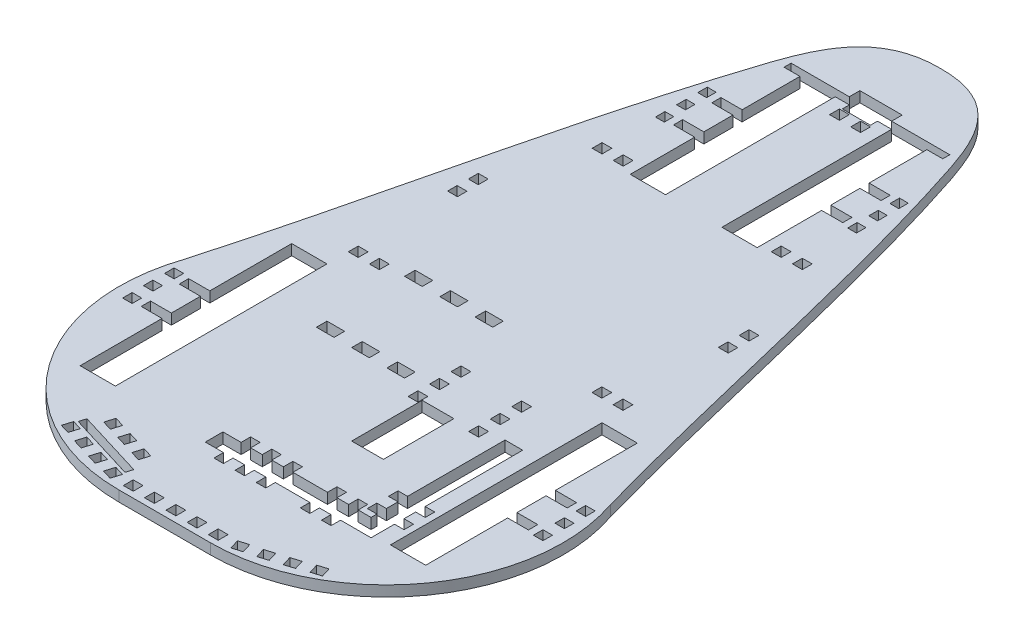
SolidWorks part; units mm, degrees
ref_plane "Front Plane" through (0, 0, 0) normal (0, 0, 1) x (1, 0, 0)
ref_plane "Top Plane" through (0, 0, 0) normal (0, 1, 0) x (1, 0, 0)
ref_plane "Right Plane" through (0, 0, 0) normal (1, 0, 0) x (0, 0, -1)
sketch "Sketch1" plane through (0, 0, 0) normal (0, 1, 0) x (1, 0, 0)
  line L0 (54.872, 210.7624) -> (54.872, -9.2376) construction
  line L1 (41.9035, -9.2376) -> (67.8405, -9.2376)
  line L6 (5.872, 75.7624) -> (15.872, 75.7624)
  line L7 (54.872, -9.2376) -> (64.872, -9.2376)
  line L8 (54.872, -9.2376) -> (44.872, -9.2376)
  line L9 (5.872, 75.7624) -> (5.872, 15.7624)
  line L10 (5.872, 15.7624) -> (15.872, 15.7624)
  line L11 (15.872, 75.7624) -> (15.872, 15.7624)
  line L12 (5.872, 75.7624) -> (15.872, 15.7624) construction
  line L13 (5.872, 15.7624) -> (15.872, 75.7624) construction
  line L18 (-0.128, 52.5374) -> (5.872, 52.5374)
  line L19 (-0.128, 52.5374) -> (-0.128, 49.8874)
  line L35 (103.872, 15.7624) -> (93.872, 15.7624)
  line L36 (93.872, 75.7624) -> (93.872, 15.7624)
  line L37 (103.872, 75.7624) -> (93.872, 75.7624)
  line L38 (103.872, 75.7624) -> (103.872, 15.7624)
  line L40 (36.872, 190.7624) -> (46.872, 190.7624)
  line L41 (36.872, 190.7624) -> (36.872, 140.7624)
  line L42 (36.872, 140.7624) -> (46.872, 140.7624)
  line L43 (46.872, 190.7624) -> (46.872, 140.7624)
  line L44 (36.872, 190.7624) -> (46.872, 140.7624) construction
  line L45 (36.872, 140.7624) -> (46.872, 190.7624) construction
  line L46 (10.872, 45.7624) -> (-10.2667, 45.7624) construction
  line L63 (72.872, 140.7624) -> (62.872, 140.7624)
  line L64 (62.872, 190.7624) -> (62.872, 140.7624)
  line L65 (72.872, 190.7624) -> (62.872, 190.7624)
  line L66 (72.872, 190.7624) -> (72.872, 140.7624)
  line L78 (114.572, 47.1124) -> (111.872, 44.4124) construction
  line L79 (114.572, 44.4124) -> (111.872, 47.1124) construction
  line L80 (114.572, 50.4124) -> (111.872, 53.1124) construction
  line L81 (114.572, 53.1124) -> (111.872, 50.4124) construction
  line L82 (109.7728, 38.9874) -> (103.7728, 41.6374) construction
  line L83 (109.7728, 41.6374) -> (103.7728, 38.9874) construction
  line L84 (109.872, 49.8874) -> (103.872, 52.5374) construction
  line L85 (109.872, 52.5374) -> (103.872, 49.8874) construction
  line L86 (111.7728, 41.1124) -> (111.7728, 38.4124)
  line L87 (114.4728, 38.4124) -> (111.7728, 38.4124)
  line L88 (114.4728, 41.1124) -> (114.4728, 38.4124)
  line L89 (111.872, 44.4124) -> (111.872, 47.1124)
  line L90 (114.572, 47.1124) -> (111.872, 47.1124)
  line L91 (114.572, 44.4124) -> (114.572, 47.1124)
  line L92 (41.872, 165.7624) -> (24.9145, 165.7624) construction
  line L93 (30.872, 172.4874) -> (36.872, 172.4874)
  line L94 (30.872, 172.4874) -> (30.872, 169.8874)
  line L95 (30.872, 169.8874) -> (36.872, 169.8874)
  line L96 (36.872, 172.4874) -> (36.872, 169.8874)
  line L97 (30.872, 172.4874) -> (36.872, 169.8874) construction
  line L98 (30.872, 169.8874) -> (36.872, 172.4874) construction
  line L103 (26.372, 161.1124) -> (28.872, 161.1124)
  line L104 (26.372, 173.1124) -> (28.872, 173.1124)
  line L105 (30.872, 161.6374) -> (36.872, 161.6374)
  line L106 (30.872, 161.6374) -> (30.872, 159.0374)
  line L107 (30.872, 159.0374) -> (36.872, 159.0374)
  line L108 (36.872, 161.6374) -> (36.872, 159.0374)
  line L109 (30.872, 161.6374) -> (36.872, 159.0374) construction
  line L110 (30.872, 159.0374) -> (36.872, 161.6374) construction
  line L111 (26.372, 173.1124) -> (26.372, 170.4124)
  line L112 (26.372, 170.4124) -> (28.872, 170.4124)
  line L113 (28.872, 173.1124) -> (28.872, 170.4124)
  line L114 (26.372, 173.1124) -> (28.872, 170.4124) construction
  line L115 (26.372, 170.4124) -> (28.872, 173.1124) construction
  line L116 (26.372, 164.4124) -> (28.872, 164.4124)
  line L117 (26.372, 164.4124) -> (26.372, 167.1124)
  line L118 (26.372, 167.1124) -> (28.872, 167.1124)
  line L119 (28.872, 164.4124) -> (28.872, 167.1124)
  line L120 (26.372, 164.4124) -> (28.872, 167.1124) construction
  line L121 (26.372, 167.1124) -> (28.872, 164.4124) construction
  line L122 (26.372, 161.1124) -> (26.372, 158.4124)
  line L123 (26.372, 158.4124) -> (28.872, 158.4124)
  line L124 (28.872, 161.1124) -> (28.872, 158.4124)
  line L125 (83.372, 167.1124) -> (80.872, 164.4124) construction
  line L126 (83.372, 164.4124) -> (80.872, 167.1124) construction
  line L127 (83.372, 170.4124) -> (80.872, 173.1124) construction
  line L128 (83.372, 173.1124) -> (80.872, 170.4124) construction
  line L129 (78.872, 159.0374) -> (72.872, 161.6374) construction
  line L130 (78.872, 161.6374) -> (72.872, 159.0374) construction
  line L131 (78.872, 169.8874) -> (72.872, 172.4874) construction
  line L132 (78.872, 172.4874) -> (72.872, 169.8874) construction
  line L133 (80.872, 161.1124) -> (80.872, 158.4124)
  line L134 (83.372, 158.4124) -> (80.872, 158.4124)
  line L135 (83.372, 161.1124) -> (83.372, 158.4124)
  line L136 (80.872, 164.4124) -> (80.872, 167.1124)
  line L137 (83.372, 167.1124) -> (80.872, 167.1124)
  line L138 (83.372, 164.4124) -> (83.372, 167.1124)
  line L139 (83.372, 164.4124) -> (80.872, 164.4124)
  line L140 (80.872, 173.1124) -> (80.872, 170.4124)
  line L141 (83.372, 170.4124) -> (80.872, 170.4124)
  line L142 (83.372, 173.1124) -> (83.372, 170.4124)
  line L143 (72.872, 161.6374) -> (72.872, 159.0374)
  line L144 (78.872, 159.0374) -> (72.872, 159.0374)
  line L145 (78.872, 161.6374) -> (78.872, 159.0374)
  line L146 (78.872, 161.6374) -> (72.872, 161.6374)
  line L147 (83.372, 173.1124) -> (80.872, 173.1124)
  line L148 (83.372, 161.1124) -> (80.872, 161.1124)
  line L149 (72.872, 172.4874) -> (72.872, 169.8874)
  line L150 (78.872, 169.8874) -> (72.872, 169.8874)
  line L151 (78.872, 172.4874) -> (78.872, 169.8874)
  line L152 (78.872, 172.4874) -> (72.872, 172.4874)
  line L153 (-0.128, 49.8874) -> (5.872, 49.8874)
  line L154 (5.872, 52.5374) -> (5.872, 49.8874)
  line L155 (-0.128, 52.5374) -> (5.872, 49.8874) construction
  line L156 (-0.128, 49.8874) -> (5.872, 52.5374) construction
  line L157 (-4.7289, 41.1124) -> (-2.0289, 41.1124)
  line L158 (-4.828, 53.1124) -> (-2.128, 53.1124)
  line L159 (-0.0289, 41.6374) -> (5.9711, 41.6374)
  line L160 (-0.0289, 41.6374) -> (-0.0289, 38.9874)
  line L161 (-0.0289, 38.9874) -> (5.9711, 38.9874)
  line L162 (5.9711, 41.6374) -> (5.9711, 38.9874)
  line L163 (-0.0289, 41.6374) -> (5.9711, 38.9874) construction
  line L164 (-0.0289, 38.9874) -> (5.9711, 41.6374) construction
  line L165 (-4.828, 53.1124) -> (-4.828, 50.4124)
  line L166 (-4.828, 50.4124) -> (-2.128, 50.4124)
  line L167 (-2.128, 53.1124) -> (-2.128, 50.4124)
  line L168 (-4.828, 53.1124) -> (-2.128, 50.4124) construction
  line L169 (-4.828, 50.4124) -> (-2.128, 53.1124) construction
  line L170 (-4.828, 44.4124) -> (-2.128, 44.4124)
  line L171 (-4.828, 44.4124) -> (-4.828, 47.1124)
  line L172 (-4.828, 47.1124) -> (-2.128, 47.1124)
  line L173 (-2.128, 44.4124) -> (-2.128, 47.1124)
  line L174 (-4.828, 44.4124) -> (-2.128, 47.1124) construction
  line L175 (-4.828, 47.1124) -> (-2.128, 44.4124) construction
  line L176 (-4.7289, 41.1124) -> (-4.7289, 38.4124)
  line L177 (-4.7289, 38.4124) -> (-2.0289, 38.4124)
  line L178 (-2.0289, 41.1124) -> (-2.0289, 38.4124)
  line L179 (114.572, 44.4124) -> (111.872, 44.4124)
  line L180 (111.872, 53.1124) -> (111.872, 50.4124)
  line L181 (114.572, 50.4124) -> (111.872, 50.4124)
  line L182 (114.572, 53.1124) -> (114.572, 50.4124)
  line L183 (103.7728, 41.6374) -> (103.7728, 38.9874)
  line L184 (109.7728, 38.9874) -> (103.7728, 38.9874)
  line L185 (109.7728, 41.6374) -> (109.7728, 38.9874)
  line L186 (109.7728, 41.6374) -> (103.7728, 41.6374)
  line L187 (114.572, 53.1124) -> (111.872, 53.1124)
  line L188 (114.4728, 41.1124) -> (111.7728, 41.1124)
  line L189 (103.872, 52.5374) -> (103.872, 49.8874)
  line L190 (109.872, 49.8874) -> (103.872, 49.8874)
  line L191 (109.872, 52.5374) -> (109.872, 49.8874)
  line L192 (109.872, 52.5374) -> (103.872, 52.5374)
  line L193 (103.872, 45.7624) -> (5.872, 45.7624) construction
  line L200 (62.872, 55.7624) -> (71.872, 55.7624)
  line L201 (62.872, 55.7624) -> (62.872, 35.7624)
  line L202 (62.872, 35.7624) -> (71.872, 35.7624)
  line L203 (71.872, 55.7624) -> (71.872, 35.7624)
  line L204 (62.872, 55.7624) -> (71.872, 35.7624) construction
  line L205 (62.872, 35.7624) -> (71.872, 55.7624) construction
  line L211 (39.9211, 61.7172) -> (44.9211, 61.7172)
  line L213 (59.9211, 69.7172) -> (62.7211, 69.7172)
  line L214 (59.9211, 57.5172) -> (62.7211, 57.5172)
  line L215 (59.9211, 57.5172) -> (59.9211, 54.7172)
  line L216 (59.9211, 54.7172) -> (62.7211, 54.7172)
  line L217 (62.7211, 57.5172) -> (62.7211, 54.7172)
  line L218 (59.9211, 57.5172) -> (62.7211, 54.7172) construction
  line L219 (59.9211, 54.7172) -> (62.7211, 57.5172) construction
  line L220 (59.9211, 69.7172) -> (59.9211, 66.9172)
  line L221 (59.9211, 66.9172) -> (62.7211, 66.9172)
  line L222 (62.7211, 69.7172) -> (62.7211, 66.9172)
  line L223 (59.9211, 63.6172) -> (62.7211, 63.6172)
  line L224 (59.9211, 63.6172) -> (59.9211, 60.8172)
  line L225 (59.9211, 60.8172) -> (62.7211, 60.8172)
  line L226 (62.7211, 63.6172) -> (62.7211, 60.8172)
  line L227 (77.1211, 69.7172) -> (79.9211, 69.7172)
  line L228 (77.1211, 57.5172) -> (79.9211, 57.5172)
  line L229 (77.1211, 57.5172) -> (77.1211, 54.7172)
  line L230 (77.1211, 54.7172) -> (79.9211, 54.7172)
  line L231 (79.9211, 57.5172) -> (79.9211, 54.7172)
  line L232 (77.1211, 69.7172) -> (77.1211, 66.9172)
  line L233 (77.1211, 66.9172) -> (79.9211, 66.9172)
  line L234 (79.9211, 69.7172) -> (79.9211, 66.9172)
  line L235 (77.1211, 63.6172) -> (79.9211, 63.6172)
  line L236 (77.1211, 63.6172) -> (77.1211, 60.8172)
  line L237 (77.1211, 60.8172) -> (79.9211, 60.8172)
  line L238 (79.9211, 63.6172) -> (79.9211, 60.8172)
  line L244 (49.9211, 61.7172) -> (54.9211, 61.7172)
  line L245 (49.9211, 61.7172) -> (49.9211, 58.7172)
  line L246 (49.9211, 58.7172) -> (54.9211, 58.7172)
  line L247 (54.9211, 61.7172) -> (54.9211, 58.7172)
  line L248 (49.9211, 61.7172) -> (54.9211, 58.7172) construction
  line L249 (49.9211, 58.7172) -> (54.9211, 61.7172) construction
  line L250 (39.9211, 61.7172) -> (39.9211, 58.7172)
  line L251 (39.9211, 58.7172) -> (44.9211, 58.7172)
  line L252 (44.9211, 61.7172) -> (44.9211, 58.7172)
  line L253 (29.9211, 61.7172) -> (34.9211, 61.7172)
  line L254 (29.9211, 61.7172) -> (29.9211, 58.7172)
  line L255 (29.9211, 58.7172) -> (34.9211, 58.7172)
  line L256 (34.9211, 61.7172) -> (34.9211, 58.7172)
  line L257 (49.9211, 86.7172) -> (54.9211, 86.7172)
  line L258 (49.9211, 86.7172) -> (49.9211, 83.7172)
  line L259 (49.9211, 83.7172) -> (54.9211, 83.7172)
  line L260 (54.9211, 86.7172) -> (54.9211, 83.7172)
  line L261 (39.9211, 86.7172) -> (44.9211, 86.7172)
  line L262 (39.9211, 86.7172) -> (39.9211, 83.7172)
  line L263 (39.9211, 83.7172) -> (44.9211, 83.7172)
  line L264 (44.9211, 86.7172) -> (44.9211, 83.7172)
  line L265 (29.9211, 86.7172) -> (34.9211, 86.7172)
  line L266 (29.9211, 86.7172) -> (29.9211, 83.7172)
  line L267 (29.9211, 83.7172) -> (34.9211, 83.7172)
  line L268 (34.9211, 86.7172) -> (34.9211, 83.7172)
  line L279 (15.072, 113.4624) -> (17.872, 113.4624)
  line L284 (15.0729, 119.4624) -> (17.8729, 119.4624)
  line L285 (15.0729, 119.4624) -> (15.0729, 116.6624)
  line L286 (15.0729, 116.6624) -> (17.8729, 116.6624)
  line L287 (17.8729, 119.4624) -> (17.8729, 116.6624)
  line L288 (15.072, 113.4624) -> (15.072, 110.7624)
  line L289 (15.072, 110.7624) -> (17.872, 110.7624)
  line L290 (17.872, 113.4624) -> (17.872, 110.7624)
  line L291 (287.5426, 108.3221) -> (290.3426, 108.3221)
  line L292 (212.3426, 111.3221) -> (290.3426, 111.3221)
  line L293 (212.3426, 111.3221) -> (212.3426, 29.7221)
  line L294 (212.3426, 29.7221) -> (290.3426, 29.7221)
  line L295 (290.3426, 111.3221) -> (290.3426, 29.7221)
  line L296 (212.3426, 108.3221) -> (215.1426, 108.3221)
  line L297 (212.3426, 108.3221) -> (212.3426, 105.5221)
  line L298 (212.3426, 105.5221) -> (215.1426, 105.5221)
  line L299 (215.1426, 108.3221) -> (215.1426, 105.5221)
  line L300 (287.5426, 108.3221) -> (287.5426, 105.5221)
  line L301 (287.5426, 105.5221) -> (290.3426, 105.5221)
  line L302 (290.3426, 108.3221) -> (290.3426, 105.5221)
  line L303 (218.3426, 108.3221) -> (221.1426, 108.3221)
  line L304 (218.3426, 108.3221) -> (218.3426, 105.5221)
  line L305 (218.3426, 105.5221) -> (221.1426, 105.5221)
  line L306 (221.1426, 108.3221) -> (221.1426, 105.5221)
  line L307 (281.5426, 84.5298) -> (284.3426, 84.5298)
  line L308 (281.5426, 84.5298) -> (281.5426, 81.7298)
  line L309 (281.5426, 81.7298) -> (284.3426, 81.7298)
  line L310 (284.3426, 84.5298) -> (284.3426, 81.7298)
  line L311 (287.5426, 35.5221) -> (290.3426, 35.5221)
  line L312 (212.3426, 35.5221) -> (215.1426, 35.5221)
  line L313 (212.3426, 35.5221) -> (212.3426, 32.7221)
  line L314 (212.3426, 32.7221) -> (215.1426, 32.7221)
  line L315 (215.1426, 35.5221) -> (215.1426, 32.7221)
  line L316 (287.5426, 35.5221) -> (287.5426, 32.7221)
  line L317 (287.5426, 32.7221) -> (290.3426, 32.7221)
  line L318 (290.3426, 35.5221) -> (290.3426, 32.7221)
  line L319 (218.3426, 35.5221) -> (221.1426, 35.5221)
  line L320 (218.3426, 35.5221) -> (218.3426, 32.7221)
  line L321 (218.3426, 32.7221) -> (221.1426, 32.7221)
  line L322 (221.1426, 35.5221) -> (221.1426, 32.7221)
  line L323 (281.5426, 35.5221) -> (284.3426, 35.5221)
  line L324 (281.5426, 35.5221) -> (281.5426, 32.7221)
  line L325 (281.5426, 32.7221) -> (284.3426, 32.7221)
  line L326 (284.3426, 35.5221) -> (284.3426, 32.7221)
  line L332 (15.9201, 84.5624) -> (18.7201, 84.5624)
  line L333 (15.9201, 84.5624) -> (15.9201, 81.7624)
  line L334 (15.9201, 81.7624) -> (18.7201, 81.7624)
  line L335 (18.7201, 84.5624) -> (18.7201, 81.7624)
  line L339 (21.9201, 84.5624) -> (24.7201, 84.5624)
  line L340 (21.9201, 84.5624) -> (21.9201, 81.7624)
  line L341 (21.9201, 81.7624) -> (24.7201, 81.7624)
  line L342 (24.7201, 84.5624) -> (24.7201, 81.7624)
  line L363 (25.072, 144.5629) -> (27.872, 144.5629)
  line L368 (25.072, 144.5629) -> (25.072, 141.7629)
  line L369 (25.072, 141.7629) -> (27.872, 141.7629)
  line L370 (27.872, 144.5629) -> (27.872, 141.7629)
  line L371 (31.072, 144.5624) -> (33.872, 144.5624)
  line L372 (31.072, 144.5624) -> (31.072, 141.7624)
  line L373 (31.072, 141.7624) -> (33.872, 141.7624)
  line L374 (33.872, 144.5624) -> (33.872, 141.7624)
  line L375 (75.872, 144.5624) -> (75.872, 141.7624)
  line L376 (78.672, 141.7624) -> (75.872, 141.7624)
  line L377 (78.672, 144.5624) -> (78.672, 141.7624)
  line L378 (78.672, 144.5624) -> (75.872, 144.5624)
  line L379 (81.872, 144.5629) -> (81.872, 141.7629)
  line L380 (84.672, 141.7629) -> (81.872, 141.7629)
  line L381 (84.672, 144.5629) -> (84.672, 141.7629)
  line L382 (84.672, 144.5629) -> (81.872, 144.5629)
  line L383 (50.4739, 186.4794) -> (50.472, 183.6794)
  line L384 (32.372, 190.884) -> (77.372, 190.884)
  line L385 (32.372, 190.884) -> (32.372, 188.884)
  line L386 (32.372, 188.884) -> (77.372, 188.884)
  line L387 (77.372, 190.884) -> (77.372, 188.884)
  line L388 (48.872, 193.884) -> (60.872, 193.884)
  line L389 (48.872, 193.884) -> (48.872, 190.884)
  line L390 (48.872, 190.884) -> (60.872, 190.884)
  line L391 (60.872, 193.884) -> (60.872, 190.884)
  line L392 (53.272, 183.6794) -> (50.472, 183.6794)
  line L393 (53.272, 186.4794) -> (53.272, 183.6794)
  line L394 (53.272, 186.4794) -> (50.4739, 186.4794)
  line L404 (85.372, 55.7624) -> (88.372, 55.7624)
  line L405 (85.372, 55.7624) -> (85.372, 15.7624)
  line L406 (85.372, 15.7624) -> (88.372, 15.7624)
  line L407 (88.372, 55.7624) -> (88.372, 15.7624)
  line L408 (44.372, 18.7624) -> (88.372, 18.7624)
  line L409 (44.372, 18.7624) -> (44.372, 15.7624)
  line L410 (44.372, 15.7624) -> (88.372, 15.7624)
  line L411 (88.372, 18.7624) -> (88.372, 15.7624)
  line L471 (41.9035, -9.2376) -> (64.872, -9.2376)
  line L480 (47.522, 22.4624) -> (47.522, 19.7624)
  line L481 (50.222, 19.7624) -> (47.522, 19.7624)
  line L482 (50.222, 22.4624) -> (50.222, 19.7624)
  line L483 (50.222, 22.4624) -> (47.522, 22.4624)
  line L484 (53.522, 22.4624) -> (53.522, 19.7624)
  line L485 (56.222, 19.7624) -> (53.522, 19.7624)
  line L486 (56.222, 22.4624) -> (56.222, 19.7624)
  line L487 (56.222, 22.4624) -> (53.522, 22.4624)
  line L488 (59.522, 22.4624) -> (59.522, 19.7624)
  line L489 (62.222, 19.7624) -> (59.522, 19.7624)
  line L490 (62.222, 22.4624) -> (62.222, 19.7624)
  line L491 (62.222, 22.4624) -> (59.522, 22.4624)
  line L492 (56.472, 186.4794) -> (59.2701, 186.4794)
  line L493 (56.472, 186.4794) -> (56.472, 183.6794)
  line L494 (56.472, 183.6794) -> (59.272, 183.6794)
  line L495 (59.2701, 186.4794) -> (59.272, 183.6794)
  line L496 (94.672, 113.4624) -> (94.672, 110.7624)
  line L497 (94.672, 110.7624) -> (91.872, 110.7624)
  line L498 (91.872, 113.4624) -> (91.872, 110.7624)
  line L499 (94.672, 113.4624) -> (91.872, 113.4624)
  line L500 (94.671, 119.4624) -> (94.671, 116.6624)
  line L501 (94.671, 116.6624) -> (91.871, 116.6624)
  line L502 (91.871, 119.4624) -> (91.871, 116.6624)
  line L503 (94.671, 119.4624) -> (91.871, 119.4624)
  line L512 (87.8238, 84.5624) -> (87.8238, 81.7624)
  line L513 (87.8238, 81.7624) -> (85.0238, 81.7624)
  line L514 (85.0238, 84.5624) -> (85.0238, 81.7624)
  line L515 (87.8238, 84.5624) -> (85.0238, 84.5624)
  line L516 (93.8238, 84.5624) -> (93.8238, 81.7624)
  line L517 (93.8238, 81.7624) -> (91.0238, 81.7624)
  line L518 (91.0238, 84.5624) -> (91.0238, 81.7624)
  line L519 (93.8238, 84.5624) -> (91.0238, 84.5624)
  line L520 (76.372, 18.7624) -> (76.372, 15.7624) construction
  line L521 (64.372, 18.7624) -> (88.372, 18.7624)
  line L522 (64.372, 18.7624) -> (64.372, 15.7624)
  line L523 (64.372, 15.7624) -> (88.372, 15.7624)
  line L524 (88.372, 18.7624) -> (88.372, 15.7624)
  line L525 (76.372, 27.5136) -> (76.372, 8.1564) construction
  line L526 (85.372, 25.7624) -> (88.372, 25.7624) construction
  line L527 (85.372, 35.7624) -> (88.372, 35.7624)
  line L528 (85.372, 35.7624) -> (85.372, 15.7624)
  line L529 (85.372, 15.7624) -> (88.372, 15.7624)
  line L530 (88.372, 35.7624) -> (88.372, 15.7624)
  line L531 (91.4767, 25.7624) -> (69.6189, 25.7624) construction
  line L532 (44.372, 17.2624) -> (64.372, 17.2624) construction
  line L537 (84.372, 57.7624) -> (89.372, 57.7624)
  line L538 (84.372, 57.7624) -> (84.372, 14.7624)
  line L539 (84.372, 14.7624) -> (89.372, 14.7624)
  line L540 (89.372, 57.7624) -> (89.372, 14.7624)
  line L541 (42.372, 19.7624) -> (89.372, 19.7624)
  line L542 (42.372, 19.7624) -> (42.372, 14.7624)
  line L543 (42.372, 14.7624) -> (89.372, 14.7624)
  line L544 (89.372, 19.7624) -> (89.372, 14.7624)
  line L545 (74.722, 14.7624) -> (74.722, 12.0624)
  line L546 (74.722, 12.0624) -> (72.022, 12.0624)
  line L547 (72.022, 14.7624) -> (72.022, 12.0624)
  line L548 (74.722, 14.7624) -> (72.022, 14.7624)
  line L553 (80.722, 14.7624) -> (80.722, 12.0624)
  line L554 (78.022, 14.7624) -> (80.722, 14.7624)
  line L555 (78.022, 14.7624) -> (78.022, 12.0624)
  line L556 (78.022, 12.0624) -> (80.722, 12.0624)
  line L557 (64.372, 17.2624) -> (88.372, 17.2624) construction
  line L558 (78.022, 19.7624) -> (80.722, 19.7624)
  line L559 (78.022, 19.7624) -> (78.022, 22.4624)
  line L560 (78.022, 22.4624) -> (80.722, 22.4624)
  line L561 (80.722, 19.7624) -> (80.722, 22.4624)
  line L562 (72.022, 19.7624) -> (72.022, 22.4624)
  line L563 (74.722, 19.7624) -> (72.022, 19.7624)
  line L564 (74.722, 19.7624) -> (74.722, 22.4624)
  line L565 (74.722, 22.4624) -> (72.022, 22.4624)
  line L566 (81.672, 27.4124) -> (84.372, 27.4124)
  line L567 (81.672, 27.4124) -> (81.672, 30.1124)
  line L568 (81.672, 30.1124) -> (84.372, 30.1124)
  line L569 (84.372, 27.4124) -> (84.372, 30.1124)
  line L574 (86.872, 35.7624) -> (86.872, 15.7624) construction
  line L575 (81.672, 24.1124) -> (81.672, 21.4124)
  line L576 (81.672, 21.4124) -> (84.372, 21.4124)
  line L577 (84.372, 24.1124) -> (84.372, 21.4124)
  line L578 (81.672, 24.1124) -> (84.372, 24.1124)
  line L579 (92.072, 24.1124) -> (89.372, 24.1124)
  line L580 (89.372, 24.1124) -> (89.372, 21.4124)
  line L581 (92.072, 21.4124) -> (89.372, 21.4124)
  line L582 (92.072, 24.1124) -> (92.072, 21.4124)
  line L583 (92.072, 27.4124) -> (92.072, 30.1124)
  line L584 (92.072, 30.1124) -> (89.372, 30.1124)
  line L585 (89.372, 27.4124) -> (89.372, 30.1124)
  line L586 (92.072, 27.4124) -> (89.372, 27.4124)
  line L588 (50.872, 188.884) -> (58.872, 188.884)
  line L589 (50.872, 188.884) -> (50.872, 186.884)
  line L590 (50.872, 186.884) -> (58.872, 186.884)
  line L591 (58.872, 188.884) -> (58.872, 186.884)
  line L659 (30.9628, 5.7849) -> (30.1441, 3.1073) construction
  line L660 (59.522, -4.7376) -> (62.322, -4.7376)
  line L661 (53.522, -4.7376) -> (56.322, -4.7376)
  line L662 (53.522, -4.7376) -> (53.522, -7.5376)
  line L663 (53.522, -7.5376) -> (56.322, -7.5376)
  line L664 (56.322, -4.7376) -> (56.322, -7.5376)
  line L665 (59.522, -4.7376) -> (59.522, -7.5376)
  line L666 (59.522, -7.5376) -> (62.322, -7.5376)
  line L667 (62.322, -4.7376) -> (62.322, -7.5376)
  line L668 (65.522, -4.7376) -> (68.322, -4.7376)
  line L669 (65.522, -4.7376) -> (65.522, -7.5376)
  line L670 (65.522, -7.5376) -> (68.322, -7.5376)
  line L671 (68.322, -4.7376) -> (68.322, -7.5376)
  line L672 (44.222, -4.7376) -> (44.222, -7.5376)
  line L673 (44.222, -7.5376) -> (41.422, -7.5376)
  line L674 (41.422, -4.7376) -> (41.422, -7.5376)
  line L675 (44.222, -4.7376) -> (41.422, -4.7376)
  line L676 (50.222, -4.7376) -> (50.222, -7.5376)
  line L677 (50.222, -7.5376) -> (47.422, -7.5376)
  line L678 (47.422, -4.7376) -> (47.422, -7.5376)
  line L679 (50.222, -4.7376) -> (47.422, -4.7376)
  line L689 (23.8861, 7.9485) -> (23.0675, 5.2708)
  line L690 (25.7451, 4.4522) -> (23.0675, 5.2708)
  line L691 (19.2847, 1.7908) -> (38.4108, -4.0567)
  line L692 (19.2847, 1.7908) -> (19.8695, 3.7034)
  line L693 (19.8695, 3.7034) -> (38.9956, -2.1441)
  line L694 (38.4108, -4.0567) -> (38.9956, -2.1441)
  line L698 (26.5638, 7.1298) -> (25.7451, 4.4522)
  line L699 (26.5638, 7.1298) -> (23.8861, 7.9485)
  line L700 (29.624, 6.1942) -> (28.8053, 3.5166)
  line L701 (31.483, 2.6979) -> (28.8053, 3.5166)
  line L702 (32.3016, 5.3756) -> (31.483, 2.6979)
  line L703 (32.3016, 5.3756) -> (29.624, 6.1942)
  line L704 (35.3618, 4.44) -> (34.5431, 1.7624)
  line L705 (37.2208, 0.9437) -> (34.5431, 1.7624)
  line L706 (38.0394, 3.6214) -> (37.2208, 0.9437)
  line L707 (38.0394, 3.6214) -> (35.3618, 4.44)
  line L708 (62.222, 12.0624) -> (59.522, 12.0624)
  line L709 (62.222, 12.0624) -> (62.222, 14.7624)
  line L710 (62.222, 14.7624) -> (59.522, 14.7624)
  line L711 (59.522, 12.0624) -> (59.522, 14.7624)
  line L712 (56.222, 12.0624) -> (53.522, 12.0624)
  line L713 (56.222, 12.0624) -> (56.222, 14.7624)
  line L714 (56.222, 14.7624) -> (53.522, 14.7624)
  line L715 (53.522, 12.0624) -> (53.522, 14.7624)
  line L716 (50.222, 12.0624) -> (47.522, 12.0624)
  line L717 (50.222, 12.0624) -> (50.222, 14.7624)
  line L718 (50.222, 14.7624) -> (47.522, 14.7624)
  line L719 (47.522, 12.0624) -> (47.522, 14.7624)
  line L720 (15.872, 15.7624) -> (15.872, -1.9267) construction
  line L721 (93.872, 15.7624) -> (93.872, -1.9267) construction
  line L722 (29.4325, 0.7797) -> (28.8478, -1.1329) construction
  line L723 (30.0855, -2.557) -> (29.2669, -5.2347)
  line L724 (31.9445, -6.0533) -> (29.2669, -5.2347)
  line L725 (32.7632, -3.3757) -> (31.9445, -6.0533)
  line L726 (32.7632, -3.3757) -> (30.0855, -2.557)
  line L727 (35.8845, -4.1111) -> (35.0659, -6.7888)
  line L728 (37.7435, -7.6074) -> (35.0659, -6.7888)
  line L729 (38.5622, -4.9297) -> (37.7435, -7.6074)
  line L730 (38.5622, -4.9297) -> (35.8845, -4.1111)
  line L731 (18.671, 1.1516) -> (21.3487, 0.3329)
  line L732 (18.671, 1.1516) -> (17.8524, -1.5261)
  line L733 (17.8524, -1.5261) -> (20.5301, -2.3447)
  line L734 (21.3487, 0.3329) -> (20.5301, -2.3447)
  line L735 (24.3477, -0.8028) -> (27.0253, -1.6215)
  line L736 (24.3477, -0.8028) -> (23.529, -3.4805)
  line L737 (23.529, -3.4805) -> (26.2067, -4.2991)
  line L738 (27.0253, -1.6215) -> (26.2067, -4.2991)
  line L739 (71.1817, -4.9297) -> (73.8594, -4.1111)
  line L740 (71.1817, -4.9297) -> (72.0004, -7.6074)
  line L741 (72.0004, -7.6074) -> (74.678, -6.7888)
  line L742 (73.8594, -4.1111) -> (74.678, -6.7888)
  line L743 (76.9808, -3.3757) -> (79.6584, -2.557)
  line L744 (76.9808, -3.3757) -> (77.7994, -6.0533)
  line L745 (77.7994, -6.0533) -> (80.4771, -5.2347)
  line L746 (79.6584, -2.557) -> (80.4771, -5.2347)
  line L747 (85.3963, -0.8028) -> (86.2149, -3.4805)
  line L748 (86.2149, -3.4805) -> (83.5372, -4.2991)
  line L749 (82.7186, -1.6215) -> (83.5372, -4.2991)
  line L750 (85.3963, -0.8028) -> (82.7186, -1.6215)
  line L751 (91.0729, 1.1516) -> (91.8915, -1.5261)
  line L752 (91.8915, -1.5261) -> (89.2139, -2.3447)
  line L753 (88.3952, 0.3329) -> (89.2139, -2.3447)
  line L754 (91.0729, 1.1516) -> (88.3952, 0.3329)
  arc A0 (41.9035, -9.2376) -> (-5.452, 56.8081) centre (41.9035, 40.7624) cw
  arc A1 (67.8405, -9.2376) -> (115.1959, 56.8081) centre (67.8405, 40.7624) ccw
  spline S0 degree 3 poles (54.872, 210.7624) (53.982, 210.7624) (36.6831, 210.353) (26.6517, 181.7608) (12.4717, 130.3178) (2.6705, 85.557) (-5.452, 56.8081) knots 0 0 0 0 0.011072 0.22144 0.460221 1 1 1 1
  spline S1 degree 3 poles (54.872, 210.7624) (55.7619, 210.7624) (73.0609, 210.353) (83.0922, 181.7608) (97.2722, 130.3178) (107.0734, 85.557) (115.1959, 56.8081) knots 0 0 0 0 0.011072 0.22144 0.460221 1 1 1 1
  point P4 (2.872, 51.2124)
  point P24 (10.872, 45.7624)
  point P30 (-3.478, 51.7624)
  point P33 (2.9711, 40.3124)
  point P40 (-3.478, 45.7624)
  point P50 (41.872, 165.7624)
  point P67 (33.872, 171.1874)
  point P82 (27.622, 171.7624)
  point P85 (33.872, 160.3374)
  point P92 (27.622, 165.7624)
  point P121 (82.122, 165.7624)
  point P122 (75.872, 160.3374)
  point P123 (82.122, 171.7624)
  point P124 (75.872, 171.1874)
  point P131 (113.222, 45.7624)
  point P132 (106.7728, 40.3124)
  point P133 (113.222, 51.7624)
  point P134 (106.872, 51.2124)
  point P141 (67.372, 45.7624)
  point P151 (61.3211, 56.1172)
  point P177 (52.4211, 60.2172)
  point P370 (31.4243, -2.9664)
  dimension "D6" = 10
  dimension "D7" = 50
  dimension "D10" = 6
  dimension "D2" = 173.1277
  dimension "D1" = 220
  dimension "D3" = 60.3239
  dimension "D4" = 10
  dimension "D5" = 10
  dimension "D8" = 60
  dimension "D9" = 6
  dimension "D11" = 25
  dimension "D12" = 2.7
  dimension "D13" = 2.7
  dimension "D14" = 2.7
  dimension "D15" = 2.7
  dimension "D16" = 2
  dimension "D17" = 2
  dimension "D18" = 39
  dimension "D19" = 2.7
  dimension "D20" = 10
  dimension "D21" = 50
  dimension "D22" = 20
  dimension "D23" = 8
  dimension "D24" = 8.25
  dimension "D25" = 0
  dimension "D26" = 0
  dimension "D27" = 3.3
  dimension "D28" = 3.3
  dimension "D29" = 8.25
  dimension "D30" = 4.125
  dimension "D31" = 2.5
  dimension "D32" = 2.7
  dimension "D33" = 2.7
  dimension "D34" = 6
  dimension "D35" = 2.6
  dimension "D36" = 8.25
  dimension "D37" = 4.125
  dimension "D38" = 2.6
  dimension "D39" = 6
  dimension "D40" = 0
  dimension "D41" = 0
  dimension "D42" = 2.5
  dimension "D43" = 2.7
  dimension "D44" = 2.5
  dimension "D45" = 2.7
  dimension "D46" = 2
  dimension "D47" = 2
  dimension "D48" = 3.3
  dimension "D49" = 2.5
  dimension "D50" = 2.7
  dimension "D51" = 3
  dimension "0.33" = 3.3
  dimension "D52" = 2
  dimension "D53" = 52
  dimension "D54" = 2
  dimension "D55" = 2.65
  dimension "D56" = 2.8
  dimension "D57" = 9
  dimension "D58" = 20
  dimension "D59" = 10
  dimension "D60" = 47
  dimension "D61" = 24
  dimension "D62" = 0
  dimension "D63" = 2.8
  dimension "D64" = 2.8
  dimension "D65" = 0
  dimension "D66" = 5
  dimension "D67" = 3
  dimension "D68" = 3
  dimension "D69" = 20
  dimension "D70" = 3.3
  dimension "D71" = 2.8
  dimension "D72" = 2.8
  dimension "D73" = 3.3
  dimension "D74" = 2.8
  dimension "D75" = 2.8
  dimension "D76" = 2.8
  dimension "D77" = 2.8
  dimension "D78" = 2.8
  dimension "D79" = 2.8
  dimension "D80" = 3.3
  dimension "D81" = 3.3
  dimension "D82" = 0
  dimension "D83" = 5
  dimension "D84" = 3
  dimension "D85" = 5
  dimension "D86" = 0
  dimension "D87" = 5
  dimension "D88" = 5
  dimension "D89" = 3
  dimension "D90" = 5
  dimension "D91" = 3
  dimension "D92" = 2.8
  dimension "D93" = 2.8
  dimension "D94" = 5
  dimension "D95" = 3
  dimension "D96" = 2.7
  dimension "D97" = 5
  dimension "D98" = 5
  dimension "D99" = 3
  dimension "D100" = 2.8
  dimension "D101" = 5
  dimension "D102" = 3.2
  dimension "D103" = 0.001
  dimension "D104" = 37
  dimension "D105" = 30
  dimension "D106" = 78
  dimension "D107" = 81.6
  dimension "D108" = 2.8
  dimension "D109" = 2.8
  dimension "D110" = 3
  dimension "D111" = 0
  dimension "D112" = 2.8
  dimension "D113" = 2.8
  dimension "D114" = 3
  dimension "D115" = 3.2
  dimension "D116" = 2.8
  dimension "D117" = 2.8
  dimension "D118" = 2.8
  dimension "D119" = 0
  dimension "D120" = 2.8
  dimension "D121" = 2.8
  dimension "D122" = 2.8
  dimension "D123" = 3.2
  dimension "D124" = 3.2
  dimension "D125" = 2.8
  dimension "D126" = 2.8
  dimension "D127" = 2.8
  dimension "D128" = 2.8
  dimension "D129" = 3.2
  dimension "D130" = 2.8
  dimension "D131" = 2.8
  dimension "D132" = 0
  dimension "D133" = 0
  dimension "D134" = 3
  dimension "D135" = 3
  dimension "D136" = 70
  dimension "D137" = 2.8
  dimension "0.28" = 2.8
  dimension "D139" = 2.8
  dimension "D140" = 2.8
  dimension "D141" = 2.8
  dimension "D142" = 2.8
  dimension "D143" = 3.2
  dimension "D144" = 3.2
  dimension "D146" = 2.8
  dimension "D147" = 5
  dimension "D148" = 43
  dimension "D149" = 5
  dimension "D150" = 3.2
  dimension "D151" = 1
  dimension "D152" = 0
  dimension "D153" = 2.8
  dimension "D154" = 2.8
  dimension "D155" = 1.6
  dimension "D156" = 2.8
  dimension "D157" = 47
  dimension "D158" = 12.5
  dimension "D159" = 4.5
  dimension "D160" = 18
  dimension "D161" = 2.5
  dimension "D162" = 3
  dimension "D163" = 45
  dimension "D164" = 2
  dimension "D165" = 22.5
  dimension "D166" = 2.8
  dimension "D167" = 12
  dimension "D168" = 3
  dimension "D169" = 0
  dimension "D170" = 6
  dimension "D171" = 2.8
  dimension "D172" = 2.8
  dimension "D173" = 0
  dimension "D174" = 0
  dimension "D175" = 0
  dimension "D176" = 1.6
  dimension "D177" = 1.7
  dimension "D178" = 2.65
  dimension "D179" = 2.7
  dimension "D180" = 2.7
  dimension "D181" = 3
  dimension "D182" = 40
  dimension "D183" = 10
  dimension "D184" = 3
  dimension "D185" = 44
  dimension "D186" = 5.5
  dimension "D187" = 0
  dimension "D188" = 0
  dimension "D189" = 2.7
  dimension "D190" = 2.7
  dimension "D191" = 1.65
  dimension "D192" = 0
  dimension "D193" = 3.2
  dimension "D194" = 1
  dimension "D195" = 20
  dimension "D196" = 3.2
  dimension "D197" = 2.8
  dimension "D198" = 2.8
  dimension "D199" = 2.8
  dimension "D200" = 2.8
  dimension "D203" = 2.8
  dimension "D205" = 0
  dimension "D210" = 2.7
  dimension "D211" = 2.7
  dimension "D212" = 2.7
  dimension "D213" = 2.7
  dimension "D214" = 2.7
  dimension "D215" = 2.7
  dimension "D216" = 1.35
  dimension "D217" = 2.7
  dimension "D218" = 2.7
  dimension "D219" = 2.7
  dimension "D220" = 2.7
  dimension "D221" = 2.7
  dimension "D222" = 2.7
  dimension "D223" = 1.65
  dimension "D224" = 0
  dimension "D225" = 2.7
  dimension "D226" = 8
  dimension "D227" = 4
  dimension "D228" = 2
  dimension "D229" = 0
  dimension "D230" = 2.8
  dimension "D231" = 2.8
  dimension "D232" = 2.8
  dimension "D233" = 2.8
  dimension "D235" = 2.8
  dimension "D236" = 3.3
  dimension "D237" = 2.7
  dimension "D238" = 2.7
  dimension "D239" = 3.3
  dimension "D241" = 1.35
  dimension "D243" = 3.2
  dimension "D244" = 2.8
  dimension "D245" = 3.2
  dimension "D247" = 2.8
  dimension "D248" = 2
  dimension "D138" = 2.8
extrude "Boss-Extrude1" add sketch "Sketch1" along normal blind 3 contours L0 S0 A0 L1 | S1 L0 L1 A1 region at (3.3293, 0, -13.1044)
